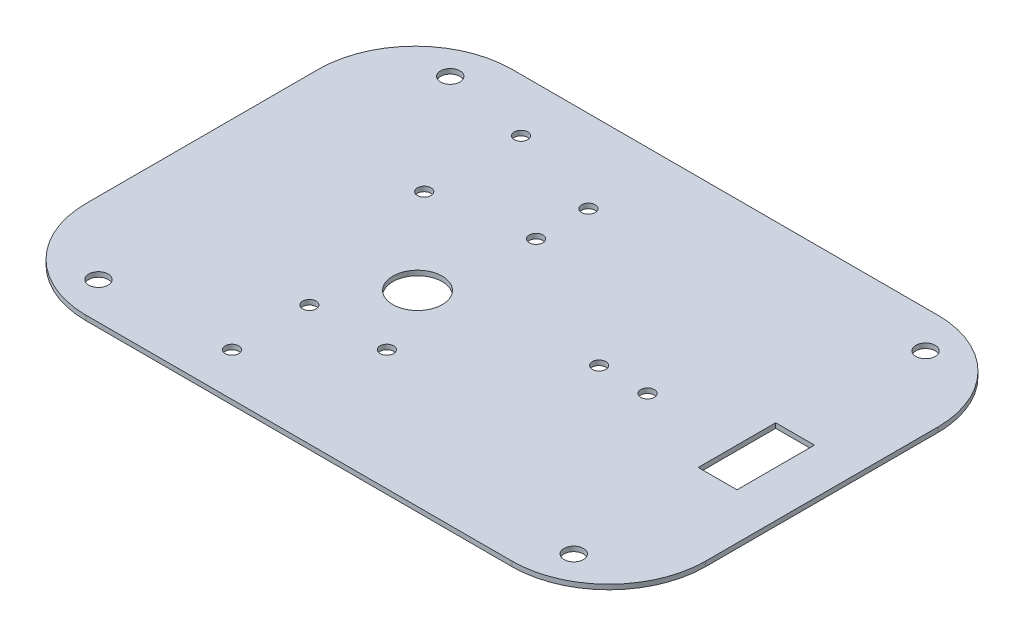
SolidWorks part; units mm, degrees
ref_plane "Front Plane" through (0, 0, 0) normal (0, 0, 1) x (1, 0, 0)
ref_plane "Top Plane" through (0, 0, 0) normal (0, 1, 0) x (1, 0, 0)
ref_plane "Right Plane" through (0, 0, 0) normal (1, 0, 0) x (0, 0, -1)
sketch "Sketch1" plane through (0, 0, 0) normal (0, 1, 0) x (1, 0, 0)
  line L2 (-160, 110) -> (160, 110)
  line L3 (-160, 110) -> (-160, -110)
  line L4 (-160, -110) -> (160, -110)
  line L5 (160, 110) -> (160, -110)
  line L6 (-160, 110) -> (160, -110) construction
  line L7 (-160, -110) -> (160, 110) construction
  point P3 (0, 0)
  dimension "D1" = 320
  dimension "D2" = 220
extrude "the upper chasiss" add sketch "Sketch1" along normal mid plane 2.5 contours L3 L2 L5 L4
sketch "Sketch2" plane through (0, 0, 0) normal (0, 1, 0) x (1, 0, 0)
  line L0 (160, 0) -> (-160, 0) construction
  line L1 (160, 110) -> (160, -110) construction
  line L2 (-160, 110) -> (-160, -110) construction
  circle A0 centre (70, 0) radius 3.5
  circle A1 centre (45, 0) radius 3.5
  dimension "D1" = 7
  dimension "D2" = 7
  dimension "D3" = 25
  dimension "D4" = 90
extrude "Battary" cut sketch "Sketch2" along normal up to surface and the other way up to surface up to face at (0, 1.25, 0) other way up to face at (0, -1.25, 0)
sketch "Sketch3" plane through (0, 0, 0) normal (0, 1, 0) x (1, 0, 0)
  line L1 (-56.8984, -47.7601) -> (-16.8984, -47.7601) construction
  line L2 (-56.8984, -47.7601) -> (-56.8984, -87.7601) construction
  circle A0 centre (-56.8984, -47.7601) radius 3.5
  circle A1 centre (-16.8984, -47.7601) radius 3.5
  circle A2 centre (-56.8984, -87.7601) radius 3.5
  point P6 (0, 0)
  point P7 (-80.3474, -25.3456)
  point P8 (-81.7268, -33.6218)
  point P9 (0, 0)
  point P10 (-72.0713, -28.1043)
  point P11 (-56.8984, -47.7601)
  dimension "D1" = 7
  dimension "D2" = 7
  dimension "D3" = 7
  dimension "D4" = 40
  dimension "D5" = 40
extrude "power section" cut sketch "Sketch3" against normal up to surface and the other way up to surface up to face at (70, -1.25, -3.5) other way up to face at (70, 1.25, -3.5)
sketch "arduino" plane through (0, 0, 0) normal (0, 1, 0) x (1, 0, 0)
  line L0 (-77.9335, 82.5888) -> (-77.9335, 32.5888) construction
  line L1 (-77.9335, 32.5888) -> (-27.9335, 40.3888) construction
  line L2 (-27.9335, 40.3888) -> (-27.9335, 67.3888) construction
  line L3 (-27.9335, 67.3888) -> (-77.9335, 82.5888) construction
  circle A0 centre (-77.9335, 82.5888) radius 3.5
  circle A1 centre (-77.9335, 32.5888) radius 3.5
  circle A2 centre (-27.9335, 67.3888) radius 3.5
  circle A3 centre (-27.9335, 40.3888) radius 3.5
  point P8 (-90.6926, 72.5885)
  point P9 (-77.9335, 82.5888)
  dimension "D1" = 7
  dimension "D2" = 7
  dimension "D3" = 7
  dimension "D4" = 7
  dimension "D5" = 50
  dimension "D6" = 27
  dimension "D7" = 50
  dimension "D8" = 15.2
extrude "arduino section" cut sketch "arduino" against normal mid plane 5
sketch "Sketch7" plane through (0, 1.25, 0) normal (0, 1, 0) x (1, 0, 0)
  line L0 (-160, 0) -> (160, 0) construction
  line L1 (-160, 110) -> (-160, -110) construction
  line L2 (160, 110) -> (160, -110) construction
  line L3 (0, 110) -> (0, -110) construction
  line L4 (-160, 110) -> (160, 110) construction
  line L5 (-160, -110) -> (160, -110) construction
  line L6 (-122.7625, -90.865) -> (-122.7625, 0) construction
  line L7 (-122.7625, 90.865) -> (-122.7625, 0) construction
  circle A2 centre (-122.7625, -90.865) radius 5
  circle A3 centre (-122.7625, 90.865) radius 5
  circle A4 centre (122.7625, -90.865) radius 5
  circle A5 centre (122.7625, 90.865) radius 5
  point P20 (0, 0)
  point P21 (-123.9772, -88.1376)
  point P22 (-122.7625, 90.865)
  dimension "D1" = 10
  dimension "D2" = 10
extrude "link nails" cut sketch "Sketch7" against normal mid plane 5
sketch "Sketch9" plane through (0, 1.25, 0) normal (0, 1, 0) x (1, 0, 0)
  line L0 (160, 0) -> (-160, 0) construction
  line L1 (160, 110) -> (160, -110) construction
  line L2 (-160, 110) -> (-160, -110) construction
  line L4 (116.2109, 20) -> (136.2109, 20)
  line L5 (116.2109, 20) -> (116.2109, -20)
  line L6 (116.2109, -20) -> (136.2109, -20)
  line L7 (136.2109, 20) -> (136.2109, -20)
  line L8 (116.2109, 20) -> (136.2109, -20) construction
  line L9 (116.2109, -20) -> (136.2109, 20) construction
  point P6 (126.2109, 0)
  point P11 (136.2109, 0)
  dimension "D1" = 20
  dimension "D2" = 40
extrude "rect cut" cut sketch "Sketch9" against normal mid plane 5
sketch "Sketch10" plane through (0, 1.25, 0) normal (0, 1, 0) x (1, 0, 0)
  circle A0 centre (-35.5184, -13.2763) radius 12.759
extrude "circ cut" cut sketch "Sketch10" against normal mid plane 5
fillet "Fillet4" radius 50 4 edges at (-160, 0, 110) (160, 0, 110) (160, 0, -110) (-160, 0, -110) first distance on face at (0, 0, 110) first distance on face at (0, 0, -110)
equation "\"carWidth\"= 22cm'the car full width"
equation "\"carLong\" = 32cm"
equation "\"D2@Sketch1\"=\"carWidth\""
equation "\"D1@Sketch1\"=\"carLong\""
equation "\"chasissTheikness\"= 0.5cm"
equation "\"D1@the upper chasiss\" = \"chasissTheikness\" / 2"
equation "\"battaryMargin\"= 25mm'the width between the two battary nails"
equation "\"battaryNailsDiam\" = 7mm'battary Nails Diameters"
equation "\"D1@Sketch2\"=\"battaryNailsDiam\""
equation "\"D2@Sketch2\"=\"battaryNailsDiam\""
equation "\"D3@Sketch2\"=\"battaryMargin\""
equation "\"powerWidht\"= 40mm"
equation "\"powerNailDiam\" = 7mm"
equation "\"D1@Sketch3\"=\"powerNailDiam\""
equation "\"D2@Sketch3\"=\"powerNailDiam\""
equation "\"D3@Sketch3\"=\"powerNailDiam\""
equation "\"D4@Sketch3\"=\"powerWidht\""
equation "\"D5@Sketch3\"=\"powerWidht\""
equation "\"arduinoTopWidth\"= 50mm'the width between nails"
equation "\"arduinoBottomWidth\"= 27mm'the width between nails"
equation "\"arduinoNailsDiam\"= 7mm'the nail diameter"
equation "\"D1@arduino\" = \"arduinoNailsDiam\""
equation "\"D2@arduino\" = \"arduinoNailsDiam\""
equation "\"D3@arduino\" = \"arduinoNailsDiam\""
equation "\"D4@arduino\" = \"arduinoNailsDiam\""
equation "\"D5@arduino\" = \"arduinoTopWidth\""
equation "\"D6@arduino\" = \"arduinoBottomWidth\""
equation "\"D7@arduino\" = \"arduinoTopWidth\""
equation "\"arduinoTobBottomShift\"= 15.2mm"
equation "\"D8@arduino\" = \"arduinoTobBottomShift\""
equation "\"chasissNailsDiam\"= 10mm"
equation "\"D2@Sketch7\"=\"chasissNailsDiam\""
equation "\"D1@Sketch7\"=\"chasissNailsDiam\""
